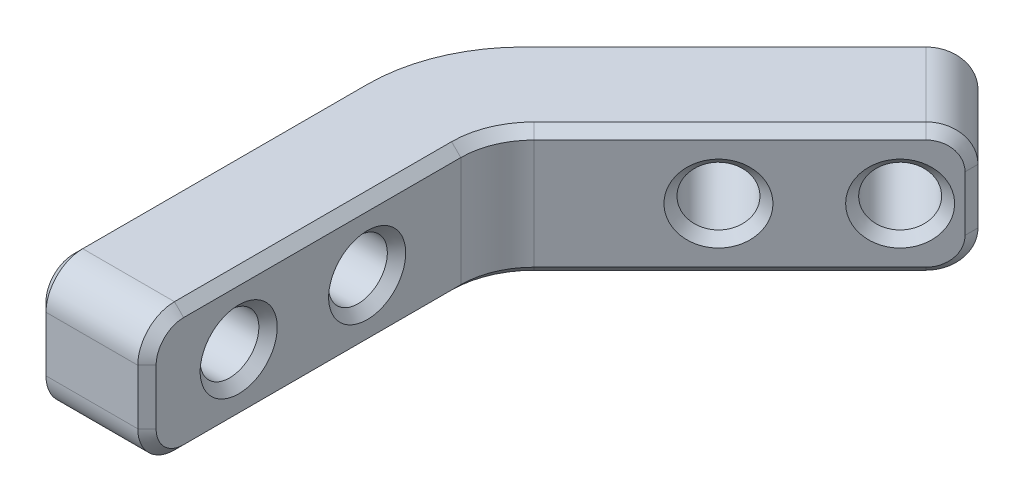
SolidWorks part; units mm, degrees
ref_plane "Front Plane" through (0, 0, 0) normal (0, 0, 1) x (1, 0, 0)
ref_plane "Top Plane" through (0, 0, 0) normal (0, 1, 0) x (1, 0, 0)
ref_plane "Right Plane" through (0, 0, 0) normal (1, 0, 0) x (0, 0, -1)
sketch "Sketch1" plane through (0, 0, 0) normal (0, 1, 0) x (1, 0, 0)
  line L0 (0, 0) -> (0, -25.4) construction
  line L1 (0, 0) -> (17.9605, 17.9605) construction
  line L2 (3.81, -1.5782) -> (3.81, -25.4)
  line L3 (3.81, -1.5782) -> (20.6546, 15.2664)
  line L4 (-3.81, 1.5782) -> (-3.81, -25.4)
  line L5 (-3.81, 1.5782) -> (15.2664, 20.6546)
  line L6 (3.81, -25.4) -> (-3.81, -25.4)
  line L7 (20.6546, 15.2664) -> (15.2664, 20.6546)
  dimension "D1" = 135
  dimension "D2" = 25.4
  dimension "D3" = 25.4
  dimension "D4" = 3.81
  dimension "D5" = 3.81
extrude "Boss-Extrude1" add sketch "Sketch1" along normal blind 8.89 contours L3 L7 L5 L4 L6 L2
sketch "Sketch2" plane through (3.81, 0, 0) normal (1, 0, 0) x (0, 0, -1)
  line L0 (-25.4, 4.445) -> (-1.5782, 4.445) construction
  line L1 (-25.4, 8.89) -> (-25.4, 0) construction
  line L2 (-1.5782, 8.89) -> (-1.5782, 0) construction
  circle A0 centre (-19.05, 4.445) radius 2.032
  circle A1 centre (-10.16, 4.445) radius 2.032
  dimension "D1" = 4.064
  dimension "D2" = 8.5818
  dimension "D3" = 8.89
extrude "Cut-Extrude1" cut sketch "Sketch2" against normal through all contours A1 | A0
sketch "Sketch3" plane through (2.6941, 0, 2.6941) normal (0.7071, 0, 0.7071) x (0.7071, 0, -0.7071)
  line L0 (1.5782, 4.445) -> (25.4, 4.445) construction
  line L1 (25.4, 8.89) -> (25.4, 0) construction
  circle A0 centre (21.59, 4.445) radius 2.032
  circle A1 centre (12.7, 4.445) radius 2.032
  dimension "D1" = 11.1218
  dimension "D3" = 4.064
  dimension "D2" = 8.89
extrude "Cut-Extrude2" cut sketch "Sketch3" against normal up to next contours A1 | A0
fillet "Fillet1" radius 2.54 4 edges at (17.9605, 0, -17.9605) (17.9605, 8.89, -17.9605) (0, 0, 25.4) (0, 8.89, 25.4)
fillet "Fillet2" radius 5.08 1 edges at (3.81, 4.445, 1.5782)
fillet "Fillet3" radius 11.43 1 edges at (-3.81, 4.445, -1.5782)
chamfer "Chamfer1" distance 0.635 angle 45 32 edges at (11.1355, 4.445, -16.5237) (4.8493, 4.445, -10.2375) (-3.81, 4.445, 17.018) (-3.81, 4.445, 8.128) (-2.9399, 8.89, -1.2178) (6.5041, 8.89, -11.8922) (14.7404, 8.1461, -20.1285) (15.2664, 4.445, -20.6546) (14.7404, 0.7439, -20.1285) (-3.81, 8.89, 13.0082) (-3.81, 8.1461, 24.6561) (-3.81, 4.445, 25.4) (-3.81, 0.7439, 24.6561) (6.5041, 0, -11.8922) (-2.9399, 0, -1.2178) (-3.81, 0, 13.0082) (3.81, 4.445, 17.018) (3.81, 4.445, 8.128) (4.1967, 8.89, 1.7383) (3.81, 8.89, 13.2712) (3.81, 8.1461, 24.6561) (3.81, 4.445, 25.4) (3.81, 0.7439, 24.6561) (3.81, 0, 13.2712) (4.1967, 0, 1.7383) (12.0782, 0, -6.6901) (20.1285, 0.7439, -14.7404) (20.6546, 4.445, -15.2664) (20.1285, 8.1461, -14.7404) (12.0782, 8.89, -6.6901) (19.3974, 4.445, -14.0092) (13.1112, 4.445, -7.723)
